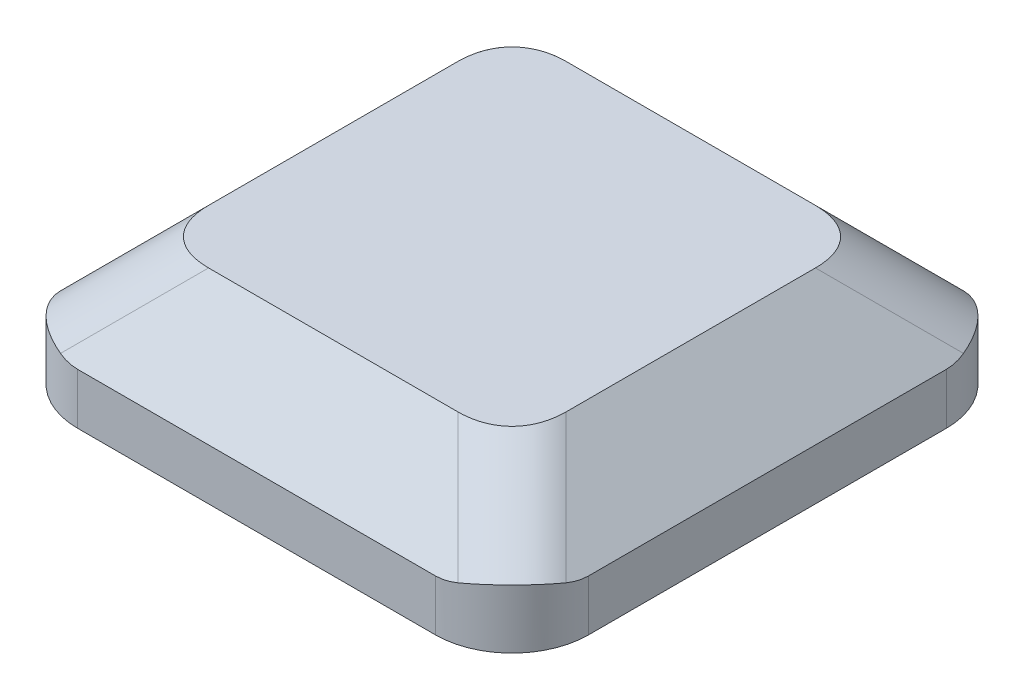
SolidWorks part; units mm, degrees
ref_plane "Front Plane" through (0, 0, 0) normal (0, 0, 1) x (1, 0, 0)
ref_plane "Top Plane" through (0, 0, 0) normal (0, 1, 0) x (1, 0, 0)
ref_plane "Right Plane" through (0, 0, 0) normal (1, 0, 0) x (0, 0, -1)
sketch "Sketch1" plane through (0, 0, 0) normal (0, 1, 0) x (1, 0, 0)
  line L1 (0, 20) -> (20, 20)
  line L2 (0, 20) -> (0, 0)
  line L3 (0, 0) -> (20, 0)
  line L4 (20, 20) -> (20, 0)
  dimension "D1" = 20
  dimension "D2" = 20
extrude "Boss-Extrude1" add sketch "Sketch1" along normal blind 5 contours L2 L1 L4 L3
chamfer "Chamfer1" distance 3 angle 45 4 edges at (0, 5, -10) (10, 5, -20) (20, 5, -10) (10, 5, 0)
fillet "Fillet1" radius 3 8 edges at (0, 1, 0) (1.5, 3.5, -1.5) (0, 1, -20) (1.5, 3.5, -18.5) (20, 1, -20) (18.5, 3.5, -18.5) (18.5, 3.5, -1.5) (20, 1, 0)
sketch "Sketch2" plane through (0, 5, 0) normal (0, 1, 0) x (1, 0, 0)
  line L0 (3, 10) -> (17, 10) construction
  line L1 (3, 14.8787) -> (3, 5.1213) construction
  line L2 (17, 5.1213) -> (17, 14.8787) construction
ref_point "Point1"
ref_axis "Axis2" through (10, 5, -10) along (0, 1, 0)
